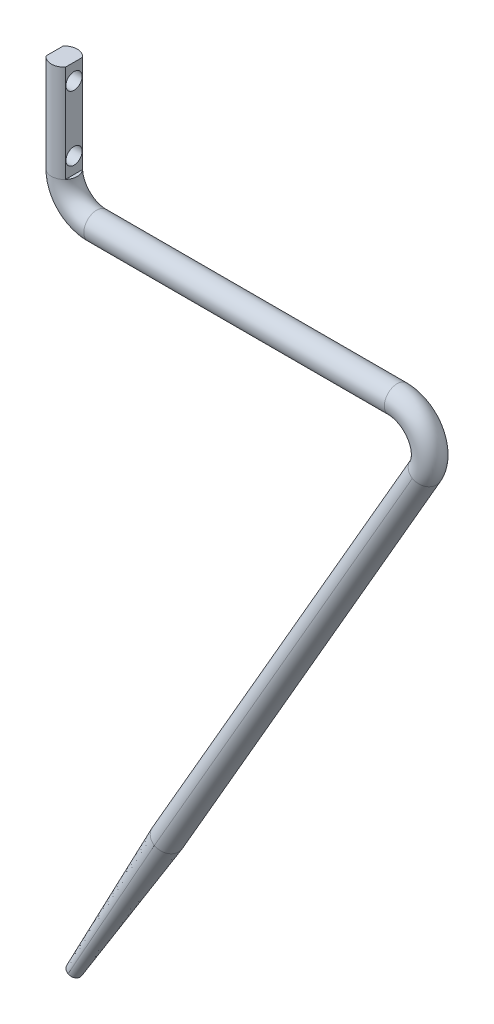
SolidWorks part; units mm, degrees
material "AISI 304"
ref_plane "前视基准面" through (0, 0, 0) normal (0, 0, 1) x (1, 0, 0)
ref_plane "上视基准面" through (0, 0, 0) normal (0, 1, 0) x (1, 0, 0)
ref_plane "右视基准面" through (0, 0, 0) normal (1, 0, 0) x (0, 0, -1)
sketch "Sketch1" plane through (0, 0, 0) normal (0, 0, 1) x (1, 0, 0)
  line L0 (0, 40) -> (0, 10)
  line L1 (10, 0) -> (102.6799, 0)
  line L2 (111.3403, -14.9998) -> (3.15, -202.4)
  arc A0 (102.6799, 0) -> (111.3403, -14.9998) centre (102.6799, -10) cw
  arc A1 (0, 10) -> (10, 0) centre (10, 10) ccw
  point P7 (120, 0)
  point P10 (0, 0)
  dimension "D5" = 10
  dimension "D1" = 40
  dimension "D2" = 120
  dimension "D3" = 202.4
  dimension "D4" = 116.85
ref_plane "Plane1" through (0, 40, 0) normal (0, 1, 0) x (1, 0, 0)
sketch "Sketch3" plane through (0, 40, 0) normal (0, 1, 0) x (1, 0, 0)
  circle A0 centre (0, 0) radius 4
  dimension "D1" = 8
sweep "Sweep1" add profiles "Sketch3" path "Sketch1"
chamfer "Chamfer1" distance 2 angle 88 1 edges at (3.15, -202.4, 4) first distance on face at (3.15, -202.4, 4)
sketch "Sketch4" plane through (0, 40, 0) normal (0, 1, 0) x (1, 0, 0)
  line L1 (3, 17.7651) -> (-3, 17.7651)
  line L2 (3, 17.7651) -> (3, -17.7651)
  line L3 (3, -17.7651) -> (-3, -17.7651)
  line L4 (-3, 17.7651) -> (-3, -17.7651)
  line L5 (3, 17.7651) -> (-3, -17.7651) construction
  line L6 (3, -17.7651) -> (-3, 17.7651) construction
  point P0 (0, 0)
  dimension "D1" = 3
extrude "Extrude1" cut sketch "Sketch4" against normal blind 30 flip side to cut
hole_wizard "M6 Tapped Hole1" positions "Sketch5" profile "Sketch6" tap size "M6" standard "GB"
sketch "Sketch5" plane through (3, 0, 0) normal (1, 0, 0) x (0, 0, -1)
  line L0 (-2.6458, 10) -> (2.6458, 10) construction
  point P0 (0, 35)
  point P2 (0, 15)
  dimension "D1" = 20
  dimension "D2" = 5
sketch "Sketch6" plane through (3, 35, 0) normal (0, 1, 0) x (0, 0, -1)
  line L0 (0, 0) -> (0, 10.5022)
  line L1 (0, 10.5022) -> (2.5, 9)
  line L2 (2.5, 9) -> (2.5, 0)
  line L5 (2.5, 0) -> (0, 0)
  line L10 (0, 10.5022) -> (-2.5, 9) construction
  line L11 (0, -6.35) -> (0, 107.95) construction
  dimension "螺纹孔钻头直径" = 5
  dimension "螺纹孔钻头深度" = 9
  dimension "导头角度" = 118
split line "Split Line1"
sketch "Sketch1<2>" plane through (0, 0, 0) normal (0, 0, 1) x (1, 0, 0) same geometry as "Sketch1"
